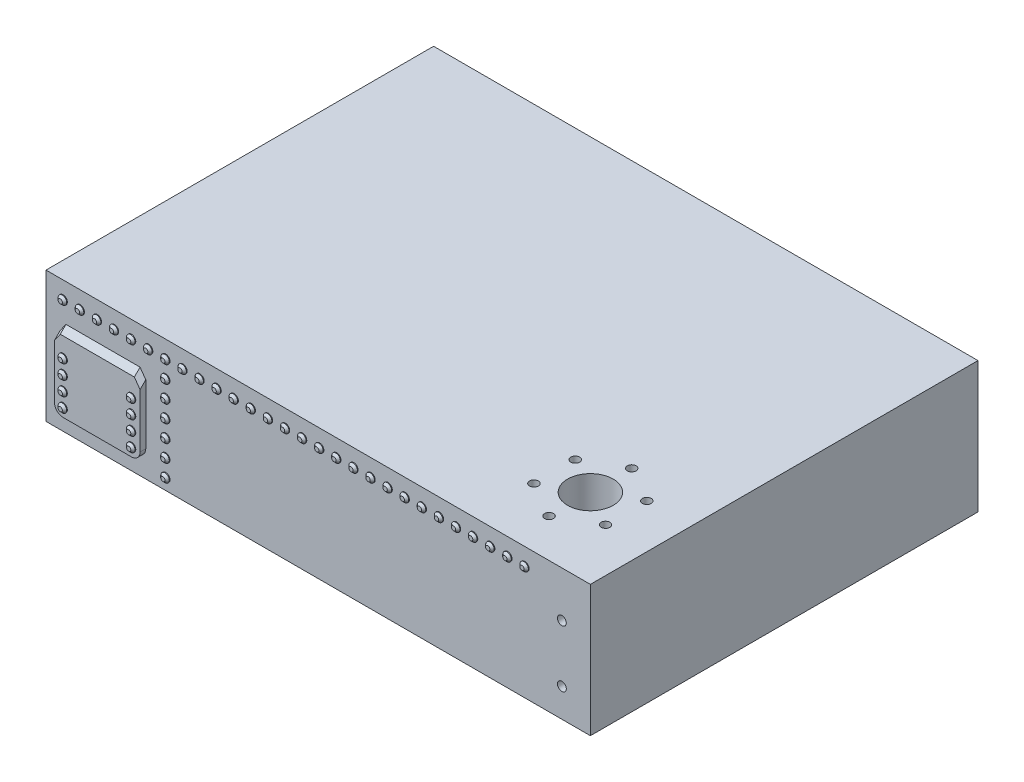
SolidWorks part; units mm, degrees
ref_plane "Front Plane" through (0, 0, 0) normal (0, 0, 1) x (1, 0, 0)
ref_plane "Top Plane" through (0, 0, 0) normal (0, 1, 0) x (1, 0, 0)
ref_plane "Right Plane" through (0, 0, 0) normal (1, 0, 0) x (0, 0, -1)
sketch "Sketch1" plane through (0, 0, 0) normal (0, 1, 0) x (1, 0, 0)
  line L1 (0, 0) -> (191, 0)
  line L2 (0, 0) -> (0, 136)
  line L3 (0, 136) -> (191, 136)
  line L4 (191, 0) -> (191, 136)
  dimension "D1" = 191
  dimension "D2" = 136
extrude "Boss-Extrude1" add sketch "Sketch1" along normal blind 46
sketch "Sketch3" plane through (0, 0, 0) normal (0, -1, 0) x (1, 0, 0)
  line L0 (0, -136) -> (0, 0) construction
  line L1 (5, -5) -> (186, -5)
  line L2 (5, -5) -> (5, -131)
  line L3 (5, -131) -> (186, -131)
  line L4 (186, -5) -> (186, -131)
  line L6 (191, -136) -> (0, -136) construction
  line L7 (191, 0) -> (191, -136) construction
  line L8 (0, 0) -> (191, 0) construction
  dimension "D1" = 5
  dimension "D2" = 5
  dimension "D3" = 5
  dimension "D4" = 5
extrude "Cut-Extrude1" cut sketch "Sketch3" against normal offset from surface (41 mm away) 5 contours L2 L3 L4 L1 up to face at (95.5, 46, -68)
ref_point "FrontLeft"
sketch "Sketch5" plane through (0, 0, -136) normal (0, 0, -1) x (-1, 0, 0)
  line L0 (-191, 46) -> (-119.5, 46)
  line L1 (-191, 46) -> (0, 46) construction
  line L2 (-119.5, 46) -> (-119.5, 0) construction
  line L3 (-191, 0) -> (0, 0) construction
  point P5 (-119.5, 23)
  dimension "D1" = 71.5
sketch "Sketch8" plane through (0, 0, 0) normal (0, 0, 1) x (1, 0, 0)
  line L1 (119.5, 46) -> (119.5, 0) construction
  line L2 (0, 46) -> (191, 46) construction
  line L3 (0, 0) -> (191, 0) construction
  point P0 (119.5, 23)
ref_point "SuspensionMountLeft"
ref_point "SuspensionMountRight"
sketch "Sketch9" plane through (0, 0, -136) normal (0, 0, -1) x (-1, 0, 0)
  line L0 (0, 46) -> (0, 0) construction
  line L1 (-5, 31) -> (-35, 31)
  line L2 (-5, 31) -> (-5, 6.2153)
  line L3 (-5, 6.2153) -> (-35, 6.2153)
  line L4 (-35, 31) -> (-35, 6.2153)
  line L5 (-191, 46) -> (0, 46) construction
  dimension "D1" = 5
  dimension "D2" = 15
  dimension "D3" = 30
extrude "Boss-Extrude2" add sketch "Sketch9" along normal blind 2
chamfer "Chamfer2" distance 2 angle 45 1 edges at (20, 31, -136)
fillet "Fillet1" radius 3 2 edges at (35, 6.2153, -137) (5, 6.2153, -137)
chamfer "Chamfer3" distance 2 angle 45 2 edges at (35, 32, -137) (5, 32, -137)
sketch "Sketch10" plane through (0, 0, 0) normal (0, 0, 1) x (1, 0, 0)
  line L4 (35, 31) -> (5, 31)
  line L5 (35, 6.2153) -> (35, 31)
  line L6 (5, 6.2153) -> (35, 6.2153)
  line L7 (5, 31) -> (5, 6.2153)
  line L8 (35, 31) -> (5, 31)
  line L9 (35, 6.2153) -> (35, 31)
  line L10 (5, 6.2153) -> (35, 6.2153)
  line L11 (5, 31) -> (5, 6.2153)
  dimension "D1" = 0
extrude "Boss-Extrude3" add sketch "Sketch10" along normal blind 2
chamfer "Chamfer4" distance 2 angle 45 1 edges at (20, 31, 0)
fillet "Fillet2" radius 3 2 edges at (35, 6.2153, 1) (5, 6.2153, 1)
chamfer "Chamfer5" distance 2 angle 45 2 edges at (35, 32, 1) (5, 32, 1)
sketch "Sketch23" plane through (0, 0, 2) normal (0, 0, 1) x (1, 0, 0)
  line L0 (8, 9.2153) -> (8, 31) construction
  line L1 (33, 31) -> (7, 31) construction
  line L2 (32, 9.2153) -> (32, 31) construction
  circle A0 centre (8, 9.2153) radius 1.5
  circle A1 centre (32, 9.2153) radius 1.5
  circle A2 centre (8, 14.2153) radius 1.5
  circle A3 centre (32, 14.2153) radius 1.5
  circle A4 centre (8, 19.2153) radius 1.5
  circle A5 centre (32, 19.2153) radius 1.5
  circle A6 centre (8, 24.2153) radius 1.5
  circle A7 centre (32, 24.2153) radius 1.5
  dimension "D1" = 3
  dimension "D2" = 3
  dimension "D3" = 4
extrude "Boss-Extrude8" add sketch "Sketch23" along normal blind 1 contours A4 | A2 | A0 | A1 | A3 | A5 | A7 | A6 region at (8, 9.2153, 2) region at (32, 9.2153, 2) region at (8, 14.2153, 2) region at (32, 14.2153, 2) region at (8, 19.2153, 2) region at (32, 19.2153, 2) region at (32, 24.2153, 2)
chamfer "Chamfer11" distance 0.75 angle 45 8 edges at (9.5, 24.2153, 3) (33.5, 9.2153, 3) (33.5, 14.2153, 3) (33.5, 19.2153, 3) (33.5, 24.2153, 3) (9.5, 9.2153, 3) (9.5, 14.2153, 3) (9.5, 19.2153, 3)
ref_plane "Plane1" through (0, 0, -68) normal (0, 0, 1) x (1, 0, 0)
mirror "Mirror1" about plane through (0, 0, -68) normal (0, 0, 1) of "Chamfer11", "Boss-Extrude8"
sketch "Sketch18" plane through (0, 41, 0) normal (0, -1, 0) x (1, 0, 0)
  line L1 (112.6585, -114) -> (114.6793, -117.5)
  line L2 (114.6793, -117.5) -> (118.7207, -117.5)
  line L3 (118.7207, -117.5) -> (120.7415, -114)
  line L4 (120.7415, -114) -> (118.7207, -110.5)
  line L5 (118.7207, -110.5) -> (114.6793, -110.5)
  line L6 (114.6793, -110.5) -> (112.6585, -114)
  line L7 (112.6585, -66) -> (114.6793, -69.5)
  line L8 (114.6793, -69.5) -> (118.7207, -69.5)
  line L9 (118.7207, -69.5) -> (120.7415, -66)
  line L10 (120.7415, -66) -> (118.7207, -62.5)
  line L11 (118.7207, -62.5) -> (114.6793, -62.5)
  line L12 (114.6793, -62.5) -> (112.6585, -66)
  line L13 (12.4585, -67) -> (14.4793, -70.5)
  line L14 (14.4793, -70.5) -> (18.5207, -70.5)
  line L15 (18.5207, -70.5) -> (20.5415, -67)
  line L16 (20.5415, -67) -> (18.5207, -63.5)
  line L17 (18.5207, -63.5) -> (14.4793, -63.5)
  line L18 (14.4793, -63.5) -> (12.4585, -67)
  line L19 (12.4585, -119.5) -> (14.4793, -123)
  line L20 (14.4793, -123) -> (18.5207, -123)
  line L21 (18.5207, -123) -> (20.5415, -119.5)
  line L22 (20.5415, -119.5) -> (18.5207, -116)
  line L23 (18.5207, -116) -> (14.4793, -116)
  line L24 (14.4793, -116) -> (12.4585, -119.5)
  circle A0 centre (116.7, -114) radius 3.5 construction
  circle A9 centre (116.7, -66) radius 3.5 construction
  circle A10 centre (16.5, -67) radius 3.5 construction
  circle A11 centre (16.5, -119.5) radius 3.5 construction
  point P41 (116.7, -114)
  point P42 (116.7, -66)
  point P43 (16.5, -67)
  point P44 (16.5, -119.5)
extrude "Boss-Extrude7" add sketch "Sketch18" along normal blind 14
sketch "Sketch19" plane through (0, 27, 0) normal (0, -1, 0) x (1, 0, 0)
  line L6 (112.6585, -66) -> (114.6793, -69.5)
  line L7 (114.6793, -69.5) -> (118.7207, -69.5)
  line L8 (118.7207, -69.5) -> (120.7415, -66)
  line L9 (120.7415, -66) -> (118.7207, -62.5)
  line L10 (118.7207, -62.5) -> (114.6793, -62.5)
  line L11 (114.6793, -62.5) -> (112.6585, -66)
  line L12 (112.6585, -66) -> (114.6793, -69.5)
  line L13 (114.6793, -69.5) -> (118.7207, -69.5)
  line L14 (118.7207, -69.5) -> (120.7415, -66)
  line L15 (120.7415, -66) -> (118.7207, -62.5)
  line L16 (118.7207, -62.5) -> (114.6793, -62.5)
  line L17 (114.6793, -62.5) -> (112.6585, -66)
  line L18 (120.7415, -114) -> (118.7207, -110.5)
  line L19 (118.7207, -110.5) -> (114.6793, -110.5)
  line L20 (114.6793, -110.5) -> (112.6585, -114)
  line L21 (112.6585, -114) -> (114.6793, -117.5)
  line L22 (114.6793, -117.5) -> (118.7207, -117.5)
  line L23 (118.7207, -117.5) -> (120.7415, -114)
  line L24 (120.7415, -114) -> (118.7207, -110.5)
  line L25 (118.7207, -110.5) -> (114.6793, -110.5)
  line L26 (114.6793, -110.5) -> (112.6585, -114)
  line L27 (112.6585, -114) -> (114.6793, -117.5)
  line L28 (114.6793, -117.5) -> (118.7207, -117.5)
  line L29 (118.7207, -117.5) -> (120.7415, -114)
  line L30 (12.4585, -119.5) -> (14.4793, -123)
  line L31 (14.4793, -123) -> (18.5207, -123)
  line L32 (18.5207, -123) -> (20.5415, -119.5)
  line L33 (20.5415, -119.5) -> (18.5207, -116)
  line L34 (18.5207, -116) -> (14.4793, -116)
  line L35 (14.4793, -116) -> (12.4585, -119.5)
  line L36 (12.4585, -119.5) -> (14.4793, -123)
  line L37 (14.4793, -123) -> (18.5207, -123)
  line L38 (18.5207, -123) -> (20.5415, -119.5)
  line L39 (20.5415, -119.5) -> (18.5207, -116)
  line L40 (18.5207, -116) -> (14.4793, -116)
  line L41 (14.4793, -116) -> (12.4585, -119.5)
  line L42 (18.5207, -63.5) -> (14.4793, -63.5)
  line L43 (20.5415, -67) -> (18.5207, -63.5)
  line L44 (18.5207, -70.5) -> (20.5415, -67)
  line L45 (14.4793, -70.5) -> (18.5207, -70.5)
  line L46 (12.4585, -67) -> (14.4793, -70.5)
  line L47 (14.4793, -63.5) -> (12.4585, -67)
  line L48 (18.5207, -63.5) -> (14.4793, -63.5)
  line L49 (20.5415, -67) -> (18.5207, -63.5)
  line L50 (18.5207, -70.5) -> (20.5415, -67)
  line L51 (14.4793, -70.5) -> (18.5207, -70.5)
  line L52 (12.4585, -67) -> (14.4793, -70.5)
  line L53 (14.4793, -63.5) -> (12.4585, -67)
  circle A0 centre (116.7, -66) radius 4.0415
  circle A1 centre (16.5, -67) radius 4.0415
  circle A2 centre (16.5, -119.5) radius 4.0415
  circle A3 centre (116.7, -114) radius 4.0415
  dimension "D1" = 0
  dimension "D2" = 0
  dimension "D3" = 0
  dimension "D4" = 0
hole_wizard "CSK for M2 Flat Head Machine Screw1" positions "Sketch21" profile "Sketch20" countersink size "M2" standard "ANSI Metric"
sketch "Sketch21" plane through (0, 27, 0) normal (0, -1, 0) x (-1, 0, 0)
  point P0 (-116.7, 114)
  point P3 (-116.7, 66)
  point P6 (-16.5, 67)
  point P9 (-16.5, 119.5)
sketch "Sketch20" plane through (116.7, 27, -114) normal (1, 0, 0) x (0, 0, -1)
  line L0 (0, 0) -> (0, 13.6009)
  line L1 (0, 13.6009) -> (1, 13)
  line L2 (1, 13) -> (1, 0.4195)
  line L3 (1, 0.4195) -> (1.5, 0)
  line L5 (1.5, 0) -> (0, 0)
  line L6 (-1, 0.4195) -> (-1.5, 0) construction
  line L10 (0, 13.6009) -> (-1, 13) construction
  line L11 (0, -6.35) -> (0, 107.95) construction
  dimension "Hole Dia." = 2
  dimension "Hole Depth" = 13
  dimension "Near C'Sink Dia." = 3
  dimension "Near C'Sink Angle" = 100
  dimension "Drill Angle" = 118
sketch "Sketch22" plane through (0, 0, 0) normal (-1, 0, 0) x (0, 0, 1)
  line L0 (0, 46) -> (0, 0) construction
  line L1 (-10, 10) -> (-80, 10)
  line L2 (-10, 10) -> (-10, 38)
  line L3 (-10, 38) -> (-80, 38)
  line L4 (-80, 10) -> (-80, 38)
  line L5 (-136, 0) -> (0, 0) construction
  line L6 (-136, 46) -> (0, 46) construction
  dimension "D1" = 10
  dimension "D2" = 10
  dimension "D3" = 8
  dimension "D4" = 70
extrude "Cut-Extrude2" [suppressed] cut sketch "Sketch22" against normal up to next
chamfer "Chamfer10" [suppressed] distance 28 angle 45
fillet "Fillet3" [suppressed] radius 3
sketch "Sketch24" plane through (0, 0, 0) normal (0, 0, 1) x (1, 0, 0)
  line L0 (0, 40) -> (191, 40) construction
  line L1 (0, 46) -> (0, 0) construction
  line L2 (191, 46) -> (191, 0) construction
  line L3 (0, 46) -> (191, 46) construction
  circle A0 centre (6, 40) radius 1.5
  circle A1 centre (12, 40) radius 1.5
  circle A2 centre (18, 40) radius 1.5
  circle A3 centre (24, 40) radius 1.5
  circle A4 centre (30, 40) radius 1.5
  circle A5 centre (36, 40) radius 1.5
  circle A6 centre (42, 40) radius 1.5
  circle A7 centre (48, 40) radius 1.5
  circle A8 centre (54, 40) radius 1.5
  circle A9 centre (60, 40) radius 1.5
  circle A10 centre (66, 40) radius 1.5
  circle A11 centre (72, 40) radius 1.5
  circle A12 centre (78, 40) radius 1.5
  circle A13 centre (84, 40) radius 1.5
  circle A14 centre (90, 40) radius 1.5
  circle A15 centre (96, 40) radius 1.5
  circle A16 centre (102, 40) radius 1.5
  circle A17 centre (108, 40) radius 1.5
  circle A18 centre (114, 40) radius 1.5
  circle A19 centre (120, 40) radius 1.5
  circle A20 centre (126, 40) radius 1.5
  circle A21 centre (132, 40) radius 1.5
  circle A22 centre (138, 40) radius 1.5
  circle A23 centre (144, 40) radius 1.5
  circle A24 centre (150, 40) radius 1.5
  circle A25 centre (156, 40) radius 1.5
  circle A26 centre (162, 40) radius 1.5
  circle A27 centre (168, 40) radius 1.5
  circle A28 centre (42, 34) radius 1.5
  circle A29 centre (42, 28) radius 1.5
  circle A30 centre (42, 22) radius 1.5
  circle A31 centre (42, 16) radius 1.5
  circle A32 centre (42, 10) radius 1.5
  circle A33 centre (42, 4) radius 1.5
  dimension "D2" = 3
  dimension "D1" = 6
  dimension "D3" = 6
  dimension "D4" = 28
  dimension "D5" = 7
extrude "Boss-Extrude9" add sketch "Sketch24" along normal blind 1
chamfer "Chamfer12" distance 0.75 angle 45 34 edges at (169.5, 40, 1) (163.5, 40, 1) (157.5, 40, 1) (151.5, 40, 1) (145.5, 40, 1) (139.5, 40, 1) (133.5, 40, 1) (127.5, 40, 1) (121.5, 40, 1) (115.5, 40, 1) (109.5, 40, 1) (103.5, 40, 1) (97.5, 40, 1) (91.5, 40, 1) (85.5, 40, 1) (79.5, 40, 1) (73.5, 40, 1) (67.5, 40, 1) (43.5, 4, 1) (43.5, 10, 1) (43.5, 16, 1) (43.5, 22, 1) (43.5, 28, 1) (43.5, 34, 1) (61.5, 40, 1) (55.5, 40, 1) (49.5, 40, 1) (43.5, 40, 1) (37.5, 40, 1) (31.5, 40, 1) (25.5, 40, 1) (19.5, 40, 1) (13.5, 40, 1) (7.5, 40, 1)
mirror "Mirror3" about plane through (0, 0, -68) normal (0, 0, 1) of "Chamfer12", "Boss-Extrude9"
sketch "Sketch25" plane through (0, 0, -131) normal (0, 0, 1) x (1, 0, 0)
  circle A0 centre (181, 30) radius 1.55 construction
  circle A1 centre (181, 10) radius 1.55 construction
  circle A2 centre (181, 30) radius 1.55
  circle A3 centre (181, 10) radius 1.55
extrude "Cut-Extrude3" cut sketch "Sketch25" against normal through all
sketch "Sketch26" plane through (0, 0, -5) normal (0, 0, -1) x (-1, 0, 0)
  circle A1 centre (-181, 10) radius 1.55
  circle A2 centre (-181, 10) radius 1.55
  circle A3 centre (-181, 30) radius 1.55
  circle A4 centre (-181, 30) radius 1.55
  dimension "D1" = 0
  dimension "D2" = 0
extrude "Cut-Extrude4" cut sketch "Sketch26" against normal through all
sketch "Sketch27" plane through (0, 46, 0) normal (0, 1, 0) x (1, 0, 0)
  line L0 (191, 0) -> (191, 136) construction
  line L1 (0, 0) -> (191, 0) construction
  circle A0 centre (163, 28) radius 1
  dimension "D1" = 2
  dimension "D2" = 28
  dimension "D3" = 28
sketch "Sketch28" plane through (0, 41, 0) normal (0, -1, 0) x (1, 0, 0)
  circle A0 centre (163, -13.5) radius 1.55 construction
  circle A1 centre (163, -28) radius 18
  circle A2 centre (163, -28) radius 18
  circle A3 centre (163, -28) radius 8
  circle A4 centre (163, -28) radius 8
  circle A5 centre (175.5574, -20.75) radius 1.55 construction
  circle A6 centre (175.5574, -35.25) radius 1.55 construction
  circle A7 centre (163, -42.5) radius 1.55 construction
  circle A8 centre (150.4426, -35.25) radius 1.55 construction
  circle A9 centre (150.4426, -20.75) radius 1.55 construction
  circle A10 centre (163, -13.5) radius 1.55
  circle A11 centre (175.5574, -20.75) radius 1.55
  circle A12 centre (175.5574, -35.25) radius 1.55
  circle A13 centre (163, -42.5) radius 1.55
  circle A14 centre (150.4426, -35.25) radius 1.55
  circle A15 centre (150.4426, -20.75) radius 1.55
  circle A17 centre (163, -28) radius 11
  circle A18 centre (163, -28) radius 11
  dimension "D1" = 0
  dimension "D2" = 0
  dimension "D3" = 0
extrude "Cut-Extrude5" cut sketch "Sketch28" against normal through all contours A13 | A12 | A11 | A10 | A15 | A14 region at (163, 41, -13.5) region at (175.5574, 41, -20.75) region at (175.5574, 41, -35.25) region at (163, 41, -42.5) region at (150.4426, 41, -35.25) region at (150.4426, 41, -20.75)
extrude "Cut-Extrude6" cut sketch "Sketch28<3>" against normal through all contours A4 region at (163, 41, -28)
sketch "Sketch28<3>" plane through (0, 41, 0) normal (0, -1, 0) x (1, 0, 0) same geometry as "Sketch28"
extrude "Boss-Extrude10" add sketch "Sketch28<4>" along normal blind 40 contours A18 A4 region at (152.3111, 41, -28)
sketch "Sketch28<4>" plane through (0, 41, 0) normal (0, -1, 0) x (1, 0, 0) same geometry as "Sketch28"
sketch "Sketch29" plane through (0, 1, 0) normal (0, -1, 0) x (1, 0, 0)
  line L0 (163, -28) -> (163, -43.0058) construction
  line L1 (163, -43.0058) -> (162, -43.0058)
  line L2 (163, -43.0058) -> (164, -43.0058)
  line L3 (164, -43.0058) -> (164, -13.0058)
  line L4 (164, -13.0058) -> (162, -13.0058)
  line L5 (162, -13.0058) -> (162, -43.0058)
  dimension "D2" = 1
  dimension "D1" = 1
  dimension "D3" = 30
extrude "Cut-Extrude7" cut sketch "Sketch29" against normal blind 20
ref_plane "Plane2" through (163, 46, -28) normal (0, 0, 1) x (1, 0, 0)
sketch "Sketch30" plane through (163, 46, -28) normal (0, 0, 1) x (1, 0, 0)
  line L0 (11, -5) -> (11, -46) construction
  line L1 (11, -45) -> (11, -5) construction
  line L2 (18, -5) -> (18, -46) construction
  line L3 (18, -5) -> (11, -25.5) construction
  line L4 (23, -5) -> (-158, -5)
  line L5 (-158, -5) -> (-158, -46)
  line L6 (-158, -46) -> (23, -46)
  line L7 (23, -46) -> (23, -5)
  line L8 (23, -5) -> (-158, -5)
  line L9 (-158, -5) -> (-158, -46)
  line L10 (-158, -46) -> (23, -46)
  line L11 (23, -46) -> (23, -5)
  line L12 (17, -7.9286) -> (12, -22.5714)
  line L13 (17, -7.9286) -> (17, -5)
  line L14 (17, -5) -> (17, -4.9)
  line L15 (12, -22.5714) -> (11, -22.5714)
  line L16 (11, -22.5714) -> (10.9, -22.5714)
  line L17 (10.9, -22.5714) -> (10.9, -4.9)
  line L18 (10.9, -4.9) -> (17, -4.9)
  dimension "D2" = 1
  dimension "D3" = 1
  dimension "D4" = 0.1
  dimension "D5" = 0.1
  dimension "D1" = 0
extrude "Boss-Extrude11" add sketch "Sketch30" along normal mid plane 3 contours L17 L16 L15 L12 L13 L8 region at (176.2325, 34.2396, -28)
ref_axis "Axis1" through (163, 46, -28) along (0, -1, 0)
pattern_circular "CirPattern1" count 6 over 360 about axis through (163, 46, -28) along (0, -1, 0) of "Boss-Extrude11"
chamfer "Chamfer13" distance 0.5 angle 45 2 edges at (174, 1, -28) (152, 1, -28)
